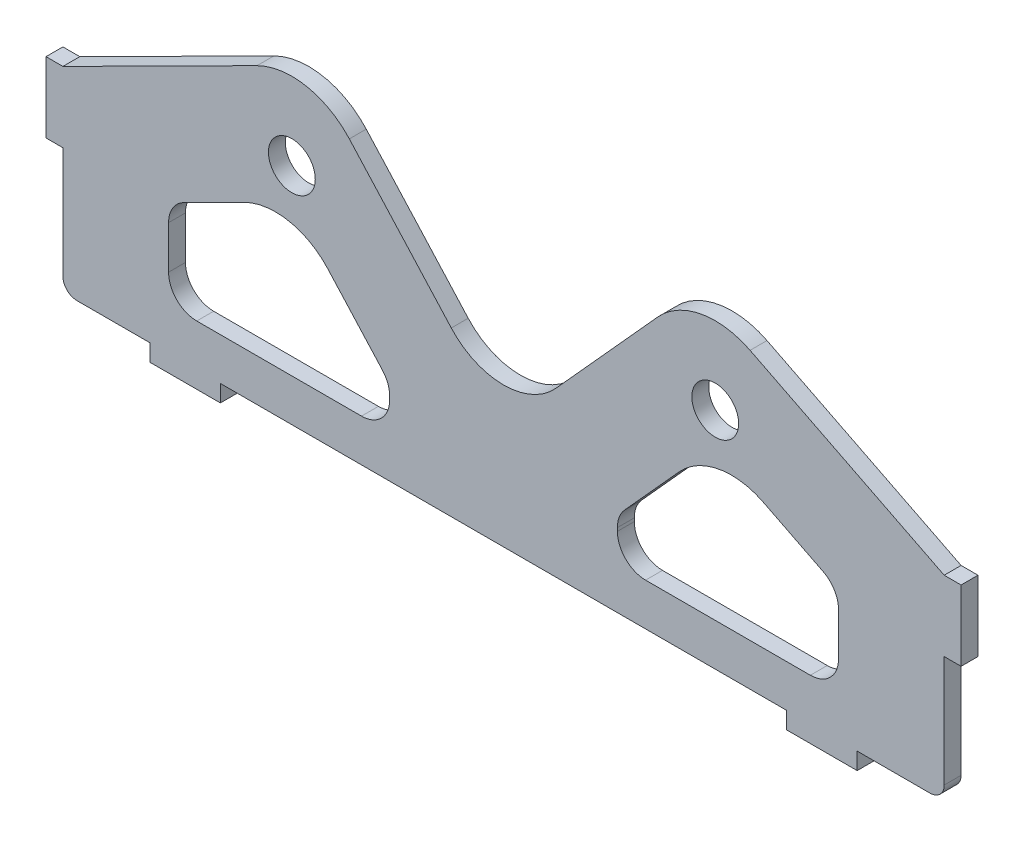
SolidWorks part; units mm, degrees
material "AISI 1020"
ref_plane "Front Plane" through (0, 0, 0) normal (0, 0, 1) x (1, 0, 0)
ref_plane "Top Plane" through (0, 0, 0) normal (0, 1, 0) x (1, 0, 0)
ref_plane "Right Plane" through (0, 0, 0) normal (1, 0, 0) x (0, 0, -1)
sketch "Sketch1" plane through (0, 0, 0) normal (0, 0, 1) x (1, 0, 0)
  line L1 (-79.4411, 35.56) -> (-79.4411, 76.0672) construction
  line L5 (51.054, 0) -> (-51.054, 0)
  line L6 (-51.054, 0) -> (-51.054, -3.048)
  line L7 (-51.054, -3.048) -> (-63.754, -3.048)
  line L8 (-63.754, -3.048) -> (-63.754, 0)
  line L9 (-63.754, 0) -> (-76.9011, 0)
  line L10 (-79.4411, 2.54) -> (-79.4411, 22.606)
  line L11 (-79.4411, 22.606) -> (-82.4891, 22.606)
  line L12 (-82.4891, 22.606) -> (-82.4891, 35.306)
  line L13 (-82.4891, 35.306) -> (-79.4411, 35.306)
  line L15 (-82.4891, 35.56) -> (-82.4891, 76.0672) construction
  line L16 (-64.008, -3.048) -> (-76.7741, -3.048) construction
  line L17 (-79.4411, 35.306) -> (-44.4469, 52.9196)
  line L18 (-27.8023, 49.8088) -> (0, 19.05)
  line L19 (-82.4891, 35.56) -> (-79.4411, 35.56) construction
  line L20 (-50.8, -3.048) -> (-50.8, 0) construction
  line L21 (-79.4411, 2.667) -> (-79.4411, 22.352) construction
  line L22 (0, -1000) -> (0, 49000) construction
  line L23 (27.8023, 49.8088) -> (0, 19.05)
  line L24 (79.4411, 35.306) -> (44.4469, 52.9196)
  line L25 (82.4891, 35.306) -> (79.4411, 35.306)
  line L26 (82.4891, 22.606) -> (82.4891, 35.306)
  line L27 (79.4411, 22.606) -> (82.4891, 22.606)
  line L28 (79.4411, 2.54) -> (79.4411, 22.606)
  line L29 (63.754, 0) -> (76.9011, 0)
  line L30 (63.754, -3.048) -> (63.754, 0)
  line L31 (51.054, -3.048) -> (63.754, -3.048)
  line L32 (51.054, 0) -> (51.054, -3.048)
  arc A0 (-27.8023, 49.8088) -> (-44.4469, 52.9196) centre (-38.1661, 40.4411) ccw
  arc A1 (-76.9011, 0) -> (-79.4411, 2.54) centre (-76.9011, 2.54) cw
  circle A2 centre (38.1661, 40.4411) radius 4.2227
  circle A3 centre (-38.1661, 40.4411) radius 4.2227
  circle A4 centre (-38.1661, 40.4411) radius 4.2227
  arc A5 (76.9011, 0) -> (79.4411, 2.54) centre (76.9011, 2.54) ccw
  arc A6 (27.8023, 49.8088) -> (44.4469, 52.9196) centre (38.1661, 40.4411) cw
  point P52 (0, 0)
  dimension "D2" = 27.94
  dimension "D7" = 2.54
  dimension "D1" = 12.7
  dimension "D4" = 19.05
  dimension "D5" = 0.254
  dimension "D6" = 0.254
  dimension "D3" = 0.254
extrude "Boss-Extrude1" add sketch "Sketch1" against normal blind 3.048 contours A2 | A4 | L17 A0 L18 L23 A6 L24 L25 L26 L27 L28 A5 L29 L30 L31 L32 L5 L6 L7 L8 L9 A1 L10 L11 L12 L13 region at (38.1661, 40.4411, 0) region at (-38.1661, 40.4411, 0)
fillet "Fillet1" radius 12.7 1 edges at (0, 19.05, -1.524)
sketch "Sketch3" plane through (0, 0, 0) normal (0, 0, 1) x (1, 0, 0)
  line L0 (-46.8091, 30.4036) -> (-60.3911, 23.5674)
  line L1 (-60.3911, 23.5674) -> (-60.3911, 7.62)
  line L2 (-60.3911, 7.62) -> (-20.5278, 7.62)
  line L3 (-20.5278, 7.62) -> (-20.5278, 15.24)
  line L4 (-20.5278, 15.24) -> (-31.6777, 27.5756)
  line L5 (-79.4411, 35.306) -> (-44.4469, 52.9196) construction
  line L6 (-27.8023, 49.8088) -> (-9.4216, 29.4735) construction
  line L7 (-79.4411, 2.54) -> (-79.4411, 22.606) construction
  line L8 (51.054, 0) -> (-51.054, 0) construction
  arc A0 (-46.8091, 30.4036) -> (-31.6777, 27.5756) centre (-41.0993, 19.0595) cw
  point P17 (-38.1661, 34.7539)
  dimension "D4" = 12.7
  dimension "D1" = 19.05
  dimension "D2" = 19.05
  dimension "D3" = 7.62
  dimension "D5" = 7.62
extrude "Cut-Extrude1" cut sketch "Sketch3" against normal through all both and the other way through all
fillet "Fillet2" radius 5.08 4 edges at (-60.3911, 7.62, -1.524) (-20.5278, 7.62, -1.524) (-20.5278, 15.24, -1.524) (-60.3911, 23.5674, -1.524)
mirror "Mirror1" about plane through (0, 0, 0) normal (1, 0, 0) of "Fillet2", "Cut-Extrude1"
equation "\"D2@Sketch3\"=\"D1@Sketch3\""
